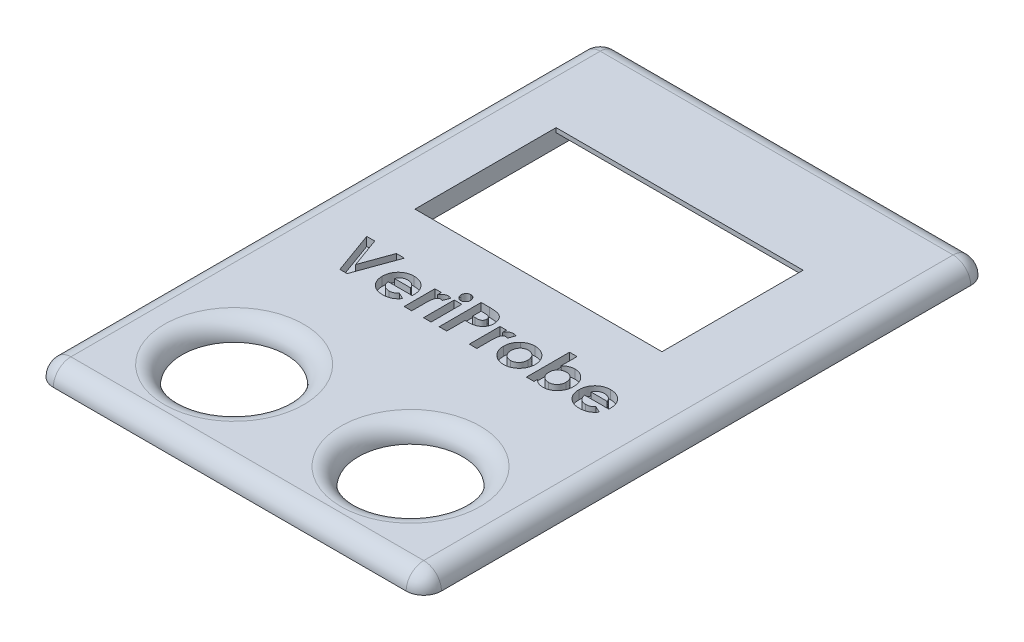
SolidWorks part; units mm, degrees
ref_plane "Front Plane" through (0, 0, 0) normal (0, 0, 1) x (1, 0, 0)
ref_plane "Top Plane" through (0, 0, 0) normal (0, 1, 0) x (1, 0, 0)
ref_plane "Right Plane" through (0, 0, 0) normal (1, 0, 0) x (0, 0, -1)
sketch "Sketch1" plane through (0, 14, 0) normal (0, 1, 0) x (1, 0, 0)
  line L4 (-22, -32) -> (22, -32)
  line L5 (22, -32) -> (22, 32)
  line L6 (22, 32) -> (-22, 32)
  line L7 (-22, 32) -> (-22, -32)
  line L8 (-22, -32) -> (22, -32)
  line L9 (22, -32) -> (22, 32)
  line L10 (22, 32) -> (-22, 32)
  line L11 (-22, 32) -> (-22, -32)
  dimension "D1" = 0
extrude "Boss-Extrude1" add sketch "Sketch1" along normal blind 2
sketch "Sketch2" plane through (0, 16, 0) normal (0, 1, 0) x (1, 0, 0)
  line L0 (22, 32) -> (-22, 32) construction
  line L1 (-15, 4) -> (13, 4)
  line L2 (-15, 4) -> (-15, 20)
  line L3 (-15, 20) -> (13, 20)
  line L4 (13, 4) -> (13, 20)
  line L5 (-15, 4) -> (13, 20) construction
  line L6 (-15, 20) -> (13, 4) construction
  line L7 (22, -32) -> (22, 32) construction
  point P0 (-1, 12)
  dimension "D1" = 28
  dimension "D2" = 16
  dimension "D3" = 12
  dimension "D4" = 9
extrude "Cut-Extrude1" cut sketch "Sketch2" against normal blind 10
sketch "Sketch3" plane through (0, 14, 0) normal (0, -1, 0) x (1, 0, 0)
  line L1 (13, -20) -> (-15, -20)
  line L2 (13, -20) -> (13, -27.5387)
  line L3 (13, -27.5387) -> (-15, -27.5387)
  line L4 (-15, -20) -> (-15, -27.5387)
extrude "Cut-Extrude2" cut sketch "Sketch3" against normal blind 1.5
sketch "Sketch4" plane through (0, 16, 0) normal (0, 1, 0) x (1, 0, 0)
  line L0 (0, -32) -> (0, -1.3082) construction
  line L1 (-22, -32) -> (22, -32) construction
  line L2 (0, -1.3082) -> (0, -32) construction
  line L3 (-22, 32) -> (-22, -32) construction
  circle A0 centre (-10, -21.5) radius 5.9
  circle A1 centre (10, -21.5) radius 5.9
  dimension "D1" = 11.8
  dimension "D2" = 12
  dimension "D3" = 10.5
extrude "Cut-Extrude3" cut sketch "Sketch4" against normal blind 6.5
fillet "Fillet2" radius 2 4 edges at (-22, 15, -32) (22, 15, -32) (22, 15, 32) (-22, 15, 32)
fillet "Fillet3" radius 2 8 edges at (-21.4142, 16, -31.4142) (0, 16, -32) (21.4142, 16, -31.4142) (22, 16, 0) (21.4142, 16, 31.4142) (0, 16, 32) (-21.4142, 16, 31.4142) (-22, 16, 0)
fillet "Fillet4" radius 2 2 edges at (10, 16, 15.6) (-10, 16, 27.4)
sketch "Sketch5" plane through (0, 16, 0) normal (0, 1, 0) x (1, 0, 0)
  text T0 "VeriProbe" font "Century Gothic" height in points 18
extrude "Cut-Extrude4" cut sketch "Sketch5" against normal blind 1
